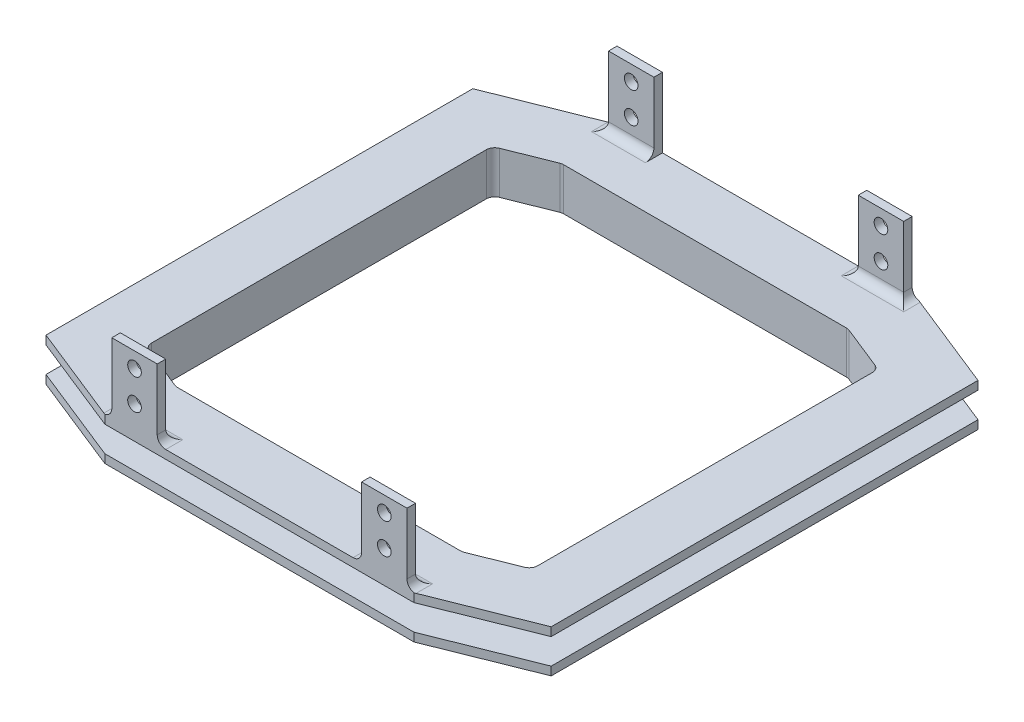
SolidWorks part; units mm, degrees
ref_plane "Front Plane" through (0, 0, 0) normal (0, 0, 1) x (1, 0, 0)
ref_plane "Top Plane" through (0, 0, 0) normal (0, 1, 0) x (1, 0, 0)
ref_plane "Right Plane" through (0, 0, 0) normal (1, 0, 0) x (0, 0, -1)
sketch "Sketch1" plane through (0, 0, 0) normal (0, 1, 0) x (1, 0, 0)
  line L5 (-35.5, 0) -> (0, 0) construction
  line L6 (-25.5, -35.5) -> (25.5, -35.5)
  line L10 (-35.5, -31.5) -> (-35.5, 31.5)
  line L11 (-25.5, 35.5) -> (25.5, 35.5)
  line L12 (35.5, -31.5) -> (35.5, 31.5)
  line L13 (0, 0) -> (0, 35.5) construction
  line L14 (25.5, -35.5) -> (35.5, -31.5)
  line L15 (25.5, 35.5) -> (35.5, 31.5)
  line L16 (-25.5, -35.5) -> (-35.5, -31.5)
  line L17 (-25.5, 35.5) -> (-35.5, 31.5)
  point P0 (0, 0)
  point P4 (35.5, -35.5)
  dimension "D3" = 4
  dimension "D2" = 10
  dimension "D4" = 71
extrude "Boss-Extrude1" add sketch "Sketch1" along normal mid plane 4.5
sketch "Sketch2" plane through (0, 2.25, 0) normal (0, 1, 0) x (1, 0, 0)
  line L16 (27.2332, -44.5) -> (44.5, -37.5933)
  line L17 (44.5, -37.5933) -> (44.5, 37.5933)
  line L18 (44.5, 37.5933) -> (27.2332, 44.5)
  line L19 (27.2332, 44.5) -> (-27.2332, 44.5)
  line L20 (-27.2332, 44.5) -> (-44.5, 37.5933)
  line L21 (-44.5, 37.5933) -> (-44.5, -37.5933)
  line L22 (-44.5, -37.5933) -> (-27.2332, -44.5)
  line L23 (-27.2332, -44.5) -> (27.2332, -44.5)
  line L24 (27.2332, -44.5) -> (44.5, -37.5933)
  line L25 (44.5, -37.5933) -> (44.5, 37.5933)
  line L26 (44.5, 37.5933) -> (27.2332, 44.5)
  line L27 (27.2332, 44.5) -> (-27.2332, 44.5)
  line L28 (-27.2332, 44.5) -> (-44.5, 37.5933)
  line L29 (-44.5, 37.5933) -> (-44.5, -37.5933)
  line L30 (-44.5, -37.5933) -> (-27.2332, -44.5)
  line L31 (-27.2332, -44.5) -> (27.2332, -44.5)
  dimension "D1" = 9
extrude "Boss-Extrude2" add sketch "Sketch2" along normal blind 1.5
mirror "Mirror1" about plane through (0, 0, 0) normal (0, 1, 0) of "Boss-Extrude2"
sketch "Sketch3" plane through (0, 0, 0) normal (0, 1, 0) x (1, 0, 0)
  line L16 (-25.2111, -34) -> (25.2111, -34)
  line L17 (25.2111, -34) -> (34, -30.4845)
  line L18 (34, -30.4845) -> (34, 30.4845)
  line L19 (34, 30.4845) -> (25.2111, 34)
  line L20 (25.2111, 34) -> (-25.2111, 34)
  line L21 (-25.2111, 34) -> (-34, 30.4845)
  line L22 (-34, 30.4845) -> (-34, -30.4845)
  line L23 (-34, -30.4845) -> (-25.2111, -34)
  line L24 (-25.2111, -34) -> (25.2111, -34)
  line L25 (25.2111, -34) -> (34, -30.4845)
  line L26 (34, -30.4845) -> (34, 30.4845)
  line L27 (34, 30.4845) -> (25.2111, 34)
  line L28 (25.2111, 34) -> (-25.2111, 34)
  line L29 (-25.2111, 34) -> (-34, 30.4845)
  line L30 (-34, 30.4845) -> (-34, -30.4845)
  line L31 (-34, -30.4845) -> (-25.2111, -34)
  dimension "D1" = 10.5
extrude "Cut-Extrude1" cut sketch "Sketch3" against normal through all both and the other way through all
sketch "Sketch5" plane through (0, 0, 0) normal (0, 0, 1) x (1, 0, 0)
  line L0 (0, 0) -> (0, 28.4264) construction
  line L1 (-27.2332, 3.75) -> (27.2332, 3.75) construction
  line L2 (-26, 3.75) -> (-18, 3.75)
  line L3 (-26, 3.75) -> (-26, 16.05)
  line L4 (-26, 16.05) -> (-18, 16.05)
  line L5 (-18, 3.75) -> (-18, 16.05)
  line L6 (-22, 16.05) -> (-22, 9.7096) construction
  line L7 (18, 3.75) -> (18, 16.05)
  line L8 (26, 16.05) -> (18, 16.05)
  line L9 (26, 3.75) -> (26, 16.05)
  line L10 (26, 3.75) -> (18, 3.75)
  dimension "D1" = 22
  dimension "D3" = 12.3
  dimension "D2" = 8
extrude "Boss-Extrude3" add sketch "Sketch5" against normal blind 1.5 from surface starting at face at (0, 3, 44.5)
extrude "Boss-Extrude4" add sketch "Sketch5<2>" along normal blind 1.5 from surface starting at face at (0, 3, -44.5)
sketch "Sketch5<2>" plane through (0, 0, 0) normal (0, 0, 1) x (1, 0, 0) same geometry as "Sketch5"
sketch "Sketch6" plane through (0, 0, 0) normal (0, 0, 1) x (1, 0, 0)
  line L0 (-22, 16.05) -> (-22, 13.35) construction
  line L1 (-18, 16.05) -> (-26, 16.05) construction
  line L2 (0, 0) -> (0, 25.5714) construction
  line L3 (-22, 13.35) -> (-22, 7.95) construction
  circle A0 centre (-22, 13.35) radius 1.2
  circle A1 centre (22, 13.35) radius 1.2
  circle A2 centre (-22, 7.95) radius 1.2
  circle A3 centre (22, 7.95) radius 1.2
  dimension "D1" = 2.4
  dimension "D2" = 2.7
  dimension "D3" = 5.4
extrude "Cut-Extrude3" cut sketch "Sketch6" against normal through all both and the other way through all
fillet "Fillet1" radius 1.5 35 edges at (35.5, 0, 31.5) (25.5, 0, 35.5) (0, 2.25, -35.5) (0, -2.25, -35.5) (35.5, 2.25, 0) (35.5, -2.25, 0) (-35.5, 2.25, 0) (-35.5, -2.25, 0) (0, 2.25, 35.5) (0, -2.25, 35.5) (-25.5, 0, -35.5) (-30.5, 2.25, -33.5) (-35.5, 0, -31.5) (-30.5, -2.25, -33.5) (35.5, 0, -31.5) (30.5, 2.25, -33.5) (25.5, 0, -35.5) (30.5, -2.25, -33.5) (30.5, 2.25, 33.5) (30.5, -2.25, 33.5) (-35.5, 0, 31.5) (-30.5, 2.25, 33.5) (-25.5, 0, 35.5) (-30.5, -2.25, 33.5) (-22, 3.75, -43) (22, 3.75, -43) (-22, 3.75, 43) (22, 3.75, 43) (26, 3.75, 43.75) (-18, 3.75, 43.75) (18, 3.75, 43.75) (-26, 3.75, 43.75) (18, 3.75, -43.75) (26, 3.75, -43.75) (-26, 3.75, -43.75)
fillet "Fillet2" radius 1.5 8 edges at (-25.2111, 0, -34) (-34, 0, -30.4845) (25.2111, 0, -34) (34, 0, -30.4845) (25.2111, 0, 34) (34, 0, 30.4845) (-25.2111, 0, 34) (-34, 0, 30.4845)
